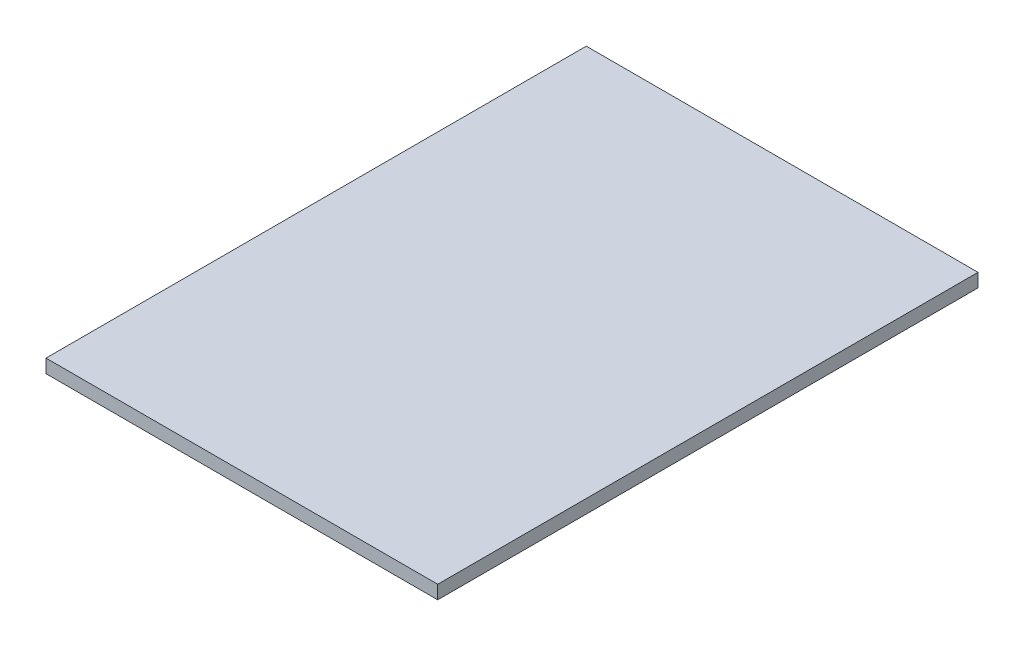
SolidWorks part; units mm, degrees
material "PBT General Purpose"
ref_plane "Front Plane" through (0, 0, 0) normal (0, 0, 1) x (1, 0, 0)
ref_plane "Top Plane" through (0, 0, 0) normal (0, 1, 0) x (1, 0, 0)
ref_plane "Right Plane" through (0, 0, 0) normal (1, 0, 0) x (0, 0, -1)
sketch "Sketch1" plane through (0, 0, 0) normal (0, 1, 0) x (1, 0, 0)
  line L1 (0, 0) -> (290, 0)
  line L2 (0, 0) -> (0, 400)
  line L3 (0, 400) -> (290, 400)
  line L4 (290, 0) -> (290, 400)
  dimension "D1" = 400
  dimension "D2" = 290
extrude "Boss-Extrude1" add sketch "Sketch1" along normal blind 10
